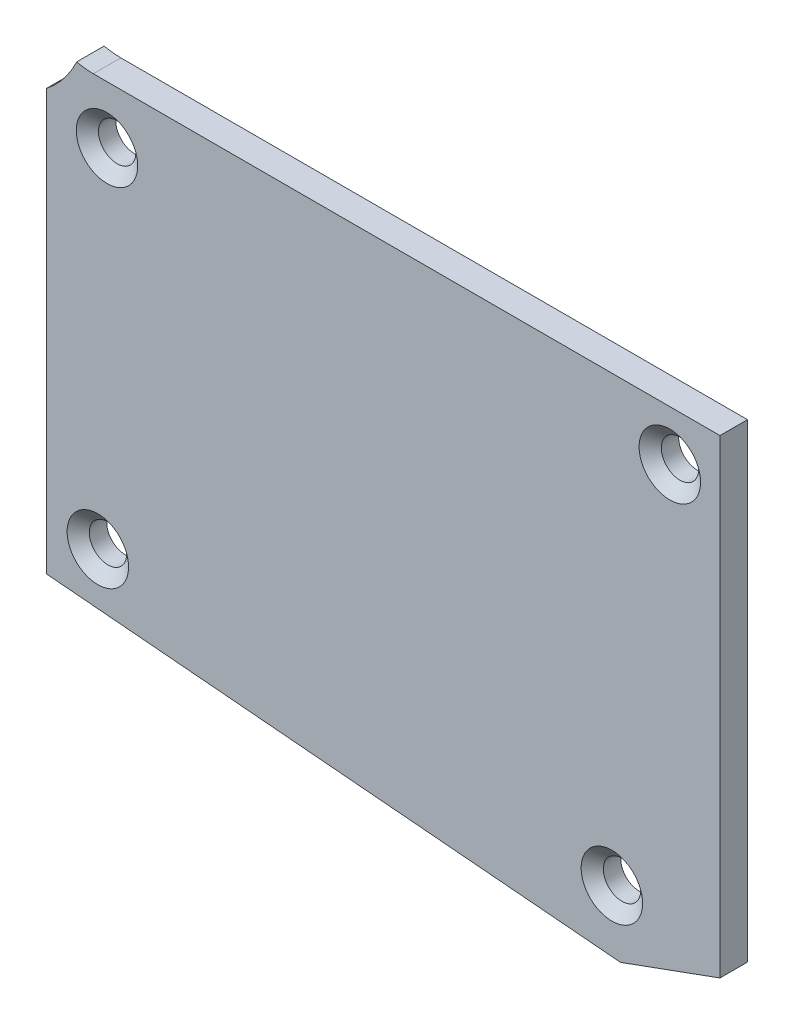
SolidWorks part; units mm, degrees
material "Acrylic (Medium-high impact)"
ref_plane "Front Plane" through (0, 0, 0) normal (0, 0, 1) x (1, 0, 0)
ref_plane "Top Plane" through (0, 0, 0) normal (0, 1, 0) x (1, 0, 0)
ref_plane "Right Plane" through (0, 0, 0) normal (1, 0, 0) x (0, 0, -1)
sketch "Sketch1" plane through (0, 0, 0) normal (0, 0, 1) x (1, 0, 0)
  line L0 (-129.2225, -27.3976) -> (-129.2225, -75.8929)
  line L1 (-129.2225, -75.8929) -> (-63.036, -81.5879)
  line L2 (-63.036, -81.5879) -> (-51.562, -77.4117)
  line L3 (-51.562, -77.4117) -> (-51.562, -23.241)
  line L4 (-51.562, -23.241) -> (-123.825, -23.241)
  line L5 (-129.9845, -27.0178) -> (-129.9845, -76.5922)
  line L6 (-129.9845, -76.5922) -> (-62.9336, -82.3615)
  line L7 (-62.9336, -82.3615) -> (-50.8, -77.9453)
  line L8 (-50.8, -77.9453) -> (-50.8, -22.479)
  line L9 (-50.8, -22.479) -> (-123.825, -22.479)
  line L10 (-129.9845, -27.0178) -> (-129.9845, -76.5922) construction
  line L11 (-129.9845, -76.5922) -> (-62.9336, -82.3615) construction
  line L12 (-62.9336, -82.3615) -> (-50.8, -77.9453) construction
  line L13 (-50.8, -77.9453) -> (-50.8, -22.479) construction
  line L14 (-50.8, -22.479) -> (-123.825, -22.479) construction
  arc A0 (-125.7469, -23.0177) -> (-123.825, -23.241) centre (-123.825, -14.859) ccw
  arc A1 (-129.2225, -27.3976) -> (-125.7469, -23.0177) centre (-136.525, -18.034) ccw
  arc A2 (-129.9845, -27.0178) -> (-126.1848, -22.1044) centre (-136.525, -18.034) ccw
  arc A3 (-126.1848, -22.1044) -> (-123.825, -22.479) centre (-123.825, -14.859) ccw
  arc A4 (-129.9845, -27.0178) -> (-126.1848, -22.1044) centre (-136.525, -18.034) ccw construction
  arc A5 (-126.1848, -22.1044) -> (-123.825, -22.479) centre (-123.825, -14.859) ccw construction
  dimension "D1" = 0
  dimension "D2" = 0.762
extrude "Boss-Extrude1" add sketch "Sketch1" along normal blind 3.175
hole_wizard "CSK for #6 Flat Head Machine Screw (100)1" positions "Sketch2" profile "Sketch3" countersink size "#6" standard "ANSI Inch" end condition up to next
sketch "Sketch2" plane through (0, 0, 3.175) normal (0, 0, 1) x (1, 0, 0)
  point P0 (-123.3005, -70.4586)
  point P3 (-122.2453, -29.8697)
  point P6 (-57.3426, -29.0216)
  point P9 (-64.0251, -74.4222)
sketch "Sketch3" plane through (-123.3005, -70.4586, 3.175) normal (1, 0, 0) x (0, -1, 0)
  line L0 (0, 0) -> (0, 3.175)
  line L1 (0, 3.175) -> (2.1526, 3.175)
  line L2 (2.1526, 3.175) -> (2.1526, 1.1669)
  line L3 (2.1526, 1.1669) -> (3.5433, 0)
  line L5 (3.5433, 0) -> (0, 0)
  line L6 (-2.1526, 1.1669) -> (-3.5433, 0) construction
  line L11 (0, -6.35) -> (0, 107.95) construction
  dimension "Thru Hole Dia." = 4.3053
  dimension "Thru Hole Depth" = 3.175
  dimension "Near C'Sink Dia." = 7.0866
  dimension "Near C'Sink Angle" = 100
